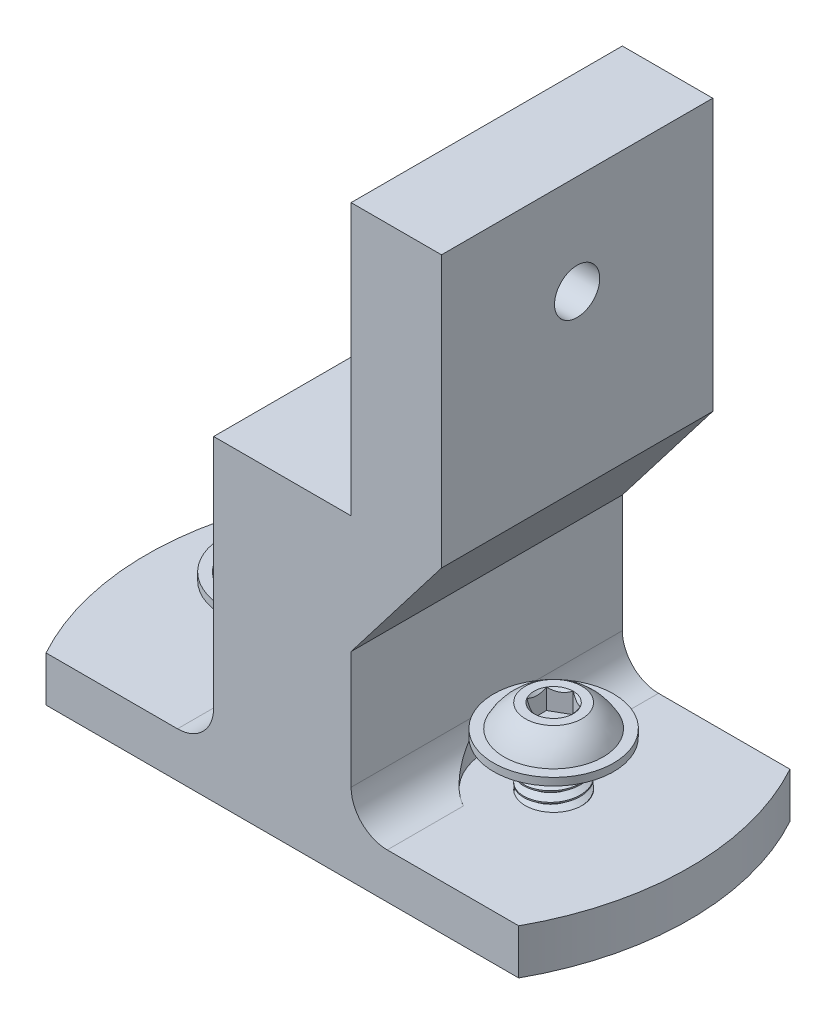
SolidWorks part; units mm, degrees
ref_plane "Front Plane" through (0, 0, 0) normal (0, 0, 1) x (1, 0, 0)
ref_plane "Top Plane" through (0, 0, 0) normal (0, 1, 0) x (1, 0, 0)
ref_plane "Right Plane" through (0, 0, 0) normal (1, 0, 0) x (0, 0, -1)
sketch "Sketch1" plane through (0, 0, 0) normal (0, 1, 0) x (1, 0, 0)
  line L0 (-19.05, 0) -> (19.05, 0) construction
  circle A0 centre (-19.05, 0) radius 3.9688
  point P3 (-23.0188, 0)
  point P4 (-15.0813, 0)
  dimension "D1" = 7.9375
  dimension "D2" = 38.1
extrude "Boss-Extrude1" add sketch "Sketch1" against normal blind 17.4625
sketch "Sketch2" plane through (0, -17.4625, 0) normal (0, -1, 0) x (1, 0, 0)
  circle A1 centre (-19.05, 0) radius 3.9688
  circle A2 centre (-19.05, 0) radius 3.9688
  point P0 (-19.05, -3.9688)
  dimension "D1" = 0
curve "Helix/Spiral1" pitch 1.4111 height 18.8736 turns 13.375
ref_plane "Plane1" through (-19.05, 0, 0) normal (1, 0, 0) x (0, 0, -1)
sketch "Sketch3" plane through (-19.05, 0, 0) normal (1, 0, 0) x (0, 0, -1)
  line L0 (4.1215, -17.3743) -> (2.8994, -18.0799) construction
  line L1 (2.8994, -18.0799) -> (4.1215, -18.7854) construction
  line L2 (4.1215, -18.7854) -> (4.1215, -17.3743) construction
  line L3 (3.0522, -17.9917) -> (3.0522, -18.1681) construction
  line L4 (3.9688, -17.4625) -> (3.9688, -18.6972) construction
  line L5 (2.8994, -18.0799) -> (3.0522, -18.0799) construction
  line L6 (3.9688, -18.0799) -> (4.1215, -18.0799) construction
  line L8 (2.8994, -18.0799) -> (-3.9688, -18.0799) construction
  line L9 (3.0522, -17.9917) -> (4.0451, -17.4184)
  line L10 (3.0522, -17.9917) -> (3.0522, -18.1681)
  line L11 (3.0522, -18.1681) -> (4.0451, -18.7413)
  line L12 (4.0451, -18.7413) -> (4.0451, -17.4184)
  line L14 (-3.9688, -18.0799) -> (-3.9688, -16.6687) construction
  line L15 (-3.9688, -16.6687) -> (-3.9688, -15.2576) construction
  line L16 (-3.9688, -15.2576) -> (-3.9687, -13.8465) construction
  line L17 (-3.9687, -13.8465) -> (-3.9688, -12.4354) construction
  line L18 (-3.9688, 0) -> (-3.9688, -17.4625) construction
  point P15 (4.0451, -18.0799)
  dimension "D1" = 1.4111
  dimension "D2" = 0.1764
sweep "Cut-Sweep1" cut profiles "Sketch3" path "Helix/Spiral1" align with end faces yes
sketch "Sketch4" plane through (0, -17.4625, 0) normal (0, -1, 0) x (1, 0, 0)
  circle A0 centre (-19.05, 0) radius 2.8994
extrude "Cut-Extrude1" cut sketch "Sketch4" against normal blind 1.4111 draft 45 flip side to cut
sketch "Sketch5" plane through (0, 0, 0) normal (0, 0, 1) x (1, 0, 0)
  line L0 (-19.05, 0) -> (-19.05, 4.2164)
  line L1 (-27.4701, 0) -> (-19.05, 0)
  line L2 (-19.05, 4.2164) -> (-23.0188, 4.2164)
  line L3 (-25.9969, 1.0541) -> (-27.4701, 1.0541)
  line L4 (-27.4701, 1.0541) -> (-27.4701, 0)
  line L5 (-19.05, 0) -> (-19.05, -17.4625) construction
  arc A0 (-23.0188, 4.2164) -> (-25.9969, 1.0541) centre (-19.05, -2.5047) ccw
  dimension "D1" = 4.2164
  dimension "D2" = 1.0541
  dimension "D3" = 16.8402
  dimension "D4" = 13.8938
revolve "Revolve1" add sketch "Sketch5" angle 360 mid plane about L0
sketch "Sketch6" plane through (0, 4.2164, 0) normal (0, 1, 0) x (1, 0, 0)
  line L1 (-19.05, 2.7496) -> (-21.4313, 1.3748)
  line L2 (-21.4313, 1.3748) -> (-21.4312, -1.3748)
  line L3 (-21.4312, -1.3748) -> (-19.05, -2.7496)
  line L4 (-19.05, -2.7496) -> (-16.6688, -1.3748)
  line L5 (-16.6688, -1.3748) -> (-16.6688, 1.3748)
  line L6 (-16.6688, 1.3748) -> (-19.05, 2.7496)
  circle A0 centre (-19.05, 0) radius 2.3813 construction
  dimension "D1" = 4.7625
extrude "Cut-Extrude2" cut sketch "Sketch6" against normal blind 2.8575
sketch "Sketch7" plane through (0, 4.2164, 0) normal (0, 1, 0) x (1, 0, 0)
  circle A0 centre (-19.05, 0) radius 2.7496
extrude "Cut-Extrude3" cut sketch "Sketch7" against normal blind 2.8575 draft 45
move or copy body "Body-Move/Copy1" bodies to move or copy 110 copy yes number of copies 1 translate (38.1, 0, 0)
sketch "Sketch8" plane through (0, 0, 0) normal (0, 1, 0) x (1, 0, 0)
  line L0 (-38.1, 0) -> (38.1, 0) construction
  line L2 (-33.1956, 19.05) -> (33.1956, 19.05)
  line L3 (-33.1956, -19.05) -> (33.1956, -19.05)
  line L4 (-38.1, 19.05) -> (38.1, 19.05) construction
  line L5 (-38.1, 19.05) -> (-38.1, -19.05) construction
  line L6 (-38.1, -19.05) -> (38.1, -19.05) construction
  line L7 (38.1, 19.05) -> (38.1, -19.05) construction
  arc A0 (-33.1956, 19.05) -> (-33.1956, -19.05) centre (1.3498, 0) ccw
  arc A1 (33.1956, 19.05) -> (33.1956, -19.05) centre (-1.3498, 0) cw
  circle A2 centre (19.05, 0) radius 3.9688
  circle A3 centre (-19.05, 0) radius 3.9688
  circle A4 centre (-19.05, 0) radius 3.9688
  dimension "D2" = 76.2
  dimension "D3" = 38.1
  dimension "D4" = 19.05
  dimension "D1" = 0
extrude "Boss-Extrude2" add sketch "Sketch8" against normal blind 6.35 from offset 6.35 separate body offset against normal yes
sketch "Sketch15" plane through (0, -6.35, 0) normal (0, 1, 0) x (1, 0, 0)
  line L0 (-10.6299, 0) -> (-10.6299, 19.05) construction
  line L1 (33.1956, 19.05) -> (-33.1956, 19.05) construction
  line L2 (10.6299, 0) -> (10.6299, 19.05) construction
  line L3 (0, 19.05) -> (-9.652, 19.05)
  line L4 (-9.652, 19.05) -> (-9.652, -19.05)
  line L5 (-33.1956, -19.05) -> (33.1956, -19.05) construction
  line L6 (0, 19.05) -> (9.652, 19.05)
  line L7 (9.652, 19.05) -> (9.652, -19.05)
  line L8 (9.652, -19.05) -> (-9.652, -19.05)
  circle A0 centre (-19.05, 0) radius 8.4201 construction
  circle A1 centre (19.05, 0) radius 8.4201 construction
extrude "Boss-Extrude7" add sketch "Sketch15" along normal blind 38.1
sketch "Sketch16" plane through (0, 31.75, 0) normal (0, 1, 0) x (1, 0, 0)
  circle A0 centre (0, 0) radius 3.175
extrude "Cut-Extrude5" cut sketch "Sketch16" against normal through all
sketch "Sketch9" plane through (0, -12.7, 0) normal (0, -1, 0) x (1, 0, 0)
  circle A0 centre (19.05, 0) radius 3.9688 construction
  circle A1 centre (-19.05, 0) radius 3.9688 construction
  circle A2 centre (-19.05, 0) radius 3.9688
  circle A3 centre (-19.05, 0) radius 4.5593
  circle A4 centre (19.05, 0) radius 3.9688
  circle A5 centre (19.05, 0) radius 4.5593
  dimension "D1" = 9.1186
sketch "SketchZ" plane through (0, 0, 0) normal (0, 0, 1) x (1, 0, 0)
  line L0 (-15.0813, -17.7271) -> (-15.0813, -16.316) construction
  line L2 (-19.05, -18.0799) -> (-19.05, -16.6687) construction
  line L4 (-15.0813, -17.7271) -> (-19.05, -17.7271) construction
  line L5 (-19.05, -13.8465) -> (-19.05, -12.4354) construction
  line L6 (-19.05, -17.3743) -> (-19.05, -18.0799) construction
sketch "Sketch19" plane through (0, -12.7, 0) normal (0, -1, 0) x (1, 0, 0)
  line L1 (0, 6.604) -> (-5.7192, 3.302)
  line L2 (-5.7192, 3.302) -> (-5.7192, -3.302)
  line L3 (-5.7192, -3.302) -> (0, -6.604)
  line L4 (0, -6.604) -> (5.7192, -3.302)
  line L5 (5.7192, -3.302) -> (5.7192, 3.302)
  line L6 (5.7192, 3.302) -> (0, 6.604)
  circle A0 centre (0, 0) radius 5.7192 construction
  dimension "D1" = 6.604
extrude "Cut-Extrude6" cut sketch "Sketch19" against normal blind 8.89
sketch "Sketch20" plane through (0, -6.35, 0) normal (0, 1, 0) x (1, 0, 0)
  circle A0 centre (19.05, 0) radius 9.398
  circle A1 centre (-19.05, 0) radius 9.398
fillet "Fillet1" radius 5.08 2 edges at (-9.652, -6.35, 0) (9.652, -6.35, 0)
extrude "Cut-Extrude7" cut sketch "Sketch20" along normal blind 12.7
sketch "Sketch21" plane through (0, 0, 19.05) normal (0, 0, 1) x (1, 0, 0)
  line L0 (9.652, 31.75) -> (22.352, 31.75) construction
  line L1 (9.652, 15.24) -> (22.352, 31.75)
  line L2 (9.652, 31.75) -> (9.652, -1.27) construction
  line L3 (22.352, 31.75) -> (22.352, 69.85)
  line L4 (9.652, 31.75) -> (9.652, 69.85)
  line L5 (9.652, 69.85) -> (22.352, 69.85)
  line L6 (9.652, 31.75) -> (9.652, 15.24)
extrude "Boss-Extrude8" add sketch "Sketch21" against normal blind 38.1
sketch "Sketch22" plane through (9.652, 0, 0) normal (-1, 0, 0) x (0, 0, 1)
  line L0 (0, 31.75) -> (0, 55.88) construction
  line L1 (19.05, 31.75) -> (-19.05, 31.75) construction
  circle A0 centre (0, 55.88) radius 3.175
  dimension "D1" = 24.13
extrude "Cut-Extrude8" cut sketch "Sketch22" against normal blind 38.1
equation "\"D3@Helix/Spiral1\" = \"D4@Helix/Spiral1\" + \"D1@Boss-Extrude1\""
equation "\"D1@Sketch3\" = \"D4@Helix/Spiral1\""
equation "\"D2@Sketch3\" = \"D1@Sketch3\" / 8"
equation "\"D1@Cut-Extrude1\" = \"D4@Helix/Spiral1\""
equation "\"D1@Cut-Extrude2\" = \"D1@Sketch6\" * 3/5"
equation "\"D1@Cut-Extrude3\" = \"D1@Cut-Extrude2\""
equation "\"D2@Sketch5\" = \"D1@Sketch5\" * 1/4"
